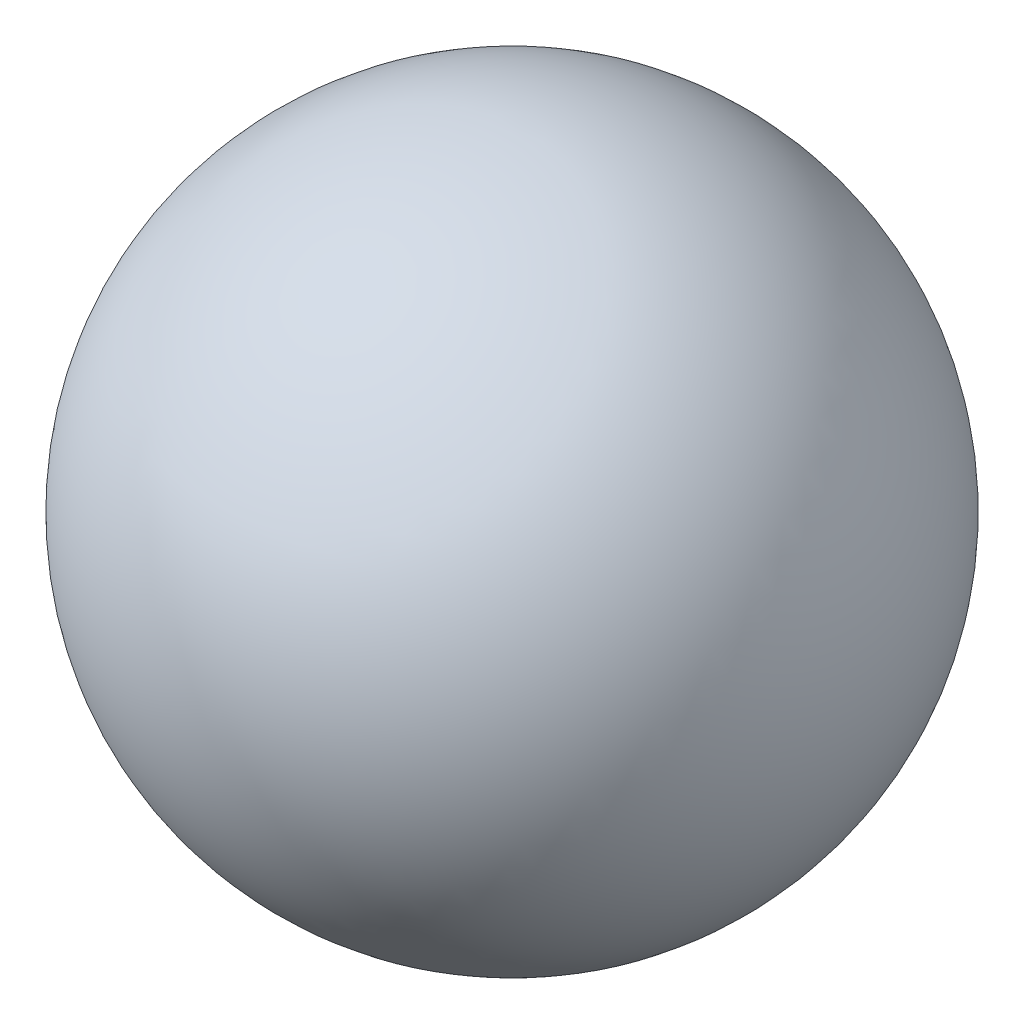
SolidWorks part; units mm, degrees
ref_plane "Front" through (0, 0, 0) normal (0, 0, 1) x (1, 0, 0)
ref_plane "Top" through (0, 0, 0) normal (0, 1, 0) x (1, 0, 0)
ref_plane "Right" through (0, 0, 0) normal (1, 0, 0) x (0, 0, -1)
sketch "Sketch2" plane through (0, 0, 0) normal (1, 0, 0) x (0, 0, -1)
  line L0 (0, -2.25) -> (0, 2.25)
  circle A0 centre (0, 0) radius 2.25 construction
  arc A1 (0, 2.25) -> (0, -2.25) centre (0, 0) cw
  dimension "D1" = 4.5
revolve "Revolve1" add sketch "Sketch2" angle 360 about L0 region at (0, 0, -0.9549)
sketch "Bearing Slot Cut Guide Loose" plane through (0, 0, 0) normal (1, 0, 0) x (0, 0, -1)
  line L0 (-1.1318, 2.35) -> (1.1318, 2.35)
  line L1 (1.1318, 2.35) -> (2.7773, 0)
  line L3 (-1.1318, 2.35) -> (-2.7773, 0)
  line L5 (0, 0) -> (0, 2.35) construction
  line L6 (0, 0) -> (-2.35, 0) construction
  line L7 (-1.1318, -2.35) -> (-2.7773, 0)
  line L8 (-1.1318, -2.35) -> (1.1318, -2.35)
  line L9 (1.1318, -2.35) -> (2.7773, 0)
  circle A3 centre (0, 0) radius 2.35 construction
  circle A5 centre (0, 0) radius 2.25 construction
  circle A6 centre (0, 0) radius 2.25 construction
  circle A7 centre (0, 0) radius 2.35 construction
  circle A8 centre (0, 0) radius 2.275 construction
  point P5 (0, 2.35)
  point P14 (2.35, 0)
  point P17 (2.7773, 0)
  point P20 (-2.7773, 0)
  point P23 (2.7773, 0)
  point P26 (-2.7773, 0)
  dimension "D1" = 4.7
  dimension "D3" = 4.55
  dimension "D2" = 55
sketch "Bearing Slot Cut Guide Tight" plane through (0, 0, 0) normal (1, 0, 0) x (0, 0, -1)
  line L20 (-1.1306, 2.35) -> (1.1306, 2.35)
  line L21 (-1.1318, 2.35) -> (1.1318, 2.35) construction
  line L22 (1.1306, 2.35) -> (2.776, 0)
  line L23 (2.776, 0) -> (1.1306, -2.35)
  line L24 (-1.1318, -2.35) -> (1.1318, -2.35) construction
  line L25 (1.1306, -2.35) -> (-1.1306, -2.35)
  line L26 (-1.1306, -2.35) -> (-2.776, 0)
  line L27 (-2.776, 0) -> (-1.1306, 2.35)
  line L28 (-1.1318, 2.35) -> (-2.7773, 0) construction
  line L29 (1.1318, 2.35) -> (2.7773, 0) construction
  line L30 (-1.1318, -2.35) -> (-2.7773, 0) construction
  line L31 (1.1318, -2.35) -> (2.7773, 0) construction
  line L32 (0, 2.35) -> (0, -2.35) construction
  dimension "D2" = 0.001
